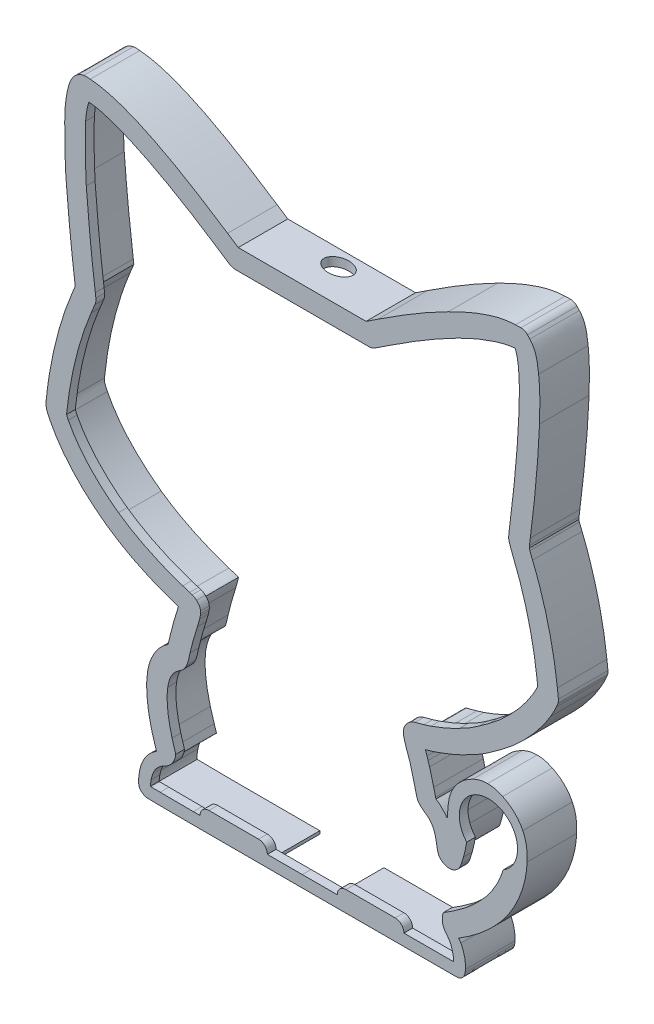
SolidWorks part; units mm, degrees
ref_plane "Front" through (0, 0, 0) normal (0, 0, 1) x (1, 0, 0)
ref_plane "Top" through (0, 0, 0) normal (0, 1, 0) x (1, 0, 0)
ref_plane "Right" through (0, 0, 0) normal (1, 0, 0) x (0, 0, -1)
sketch "Mech_Outlines_Cat" plane through (0, 0, 0) normal (0, 0, 1) x (1, 0, 0)
  line L0 (9.9633, 69.1549) -> (10.0093, 68.7865)
  line L1 (10.0093, 68.7865) -> (9.5041, 67.5722)
  line L4 (75.401, -1.0986) -> (48.9706, -1.125)
  line L6 (76.9457, 0.7665) -> (76.9132, 0.3114)
  line L8 (72.1076, 30.6075) -> (70.8601, 30.2154)
  line L10 (92.8011, 48.1756) -> (92.5648, 47.5932)
  line L12 (92.7273, 50.4965) -> (92.9034, 48.9145)
  line L15 (87.5993, 100.3815) -> (88.0029, 99.9501)
  line L18 (85.548, 100.8461) -> (86.4656, 100.8616)
  line L19 (61.947, 89.8796) -> (59.9011, 88.536)
  line L20 (59.9011, 88.536) -> (48.9353, 88.536)
  line L21 (48.9353, 88.536) -> (37.9736, 88.536)
  line L22 (37.9736, 88.536) -> (36.1471, 89.7448)
  line L26 (13.5479, 68.8251) -> (13.4504, 69.5965)
  line L29 (12.7494, 66.2211) -> (13.4097, 67.8086)
  line L31 (73.1045, 2.4142) -> (48.9672, 2.3905)
  line L35 (71.0037, 33.9449) -> (69.8057, 33.5683)
  line L36 (89.2861, 48.8458) -> (89.354, 49.0282)
  line L37 (89.354, 49.0282) -> (89.2335, 50.1084)
  line L43 (61.4513, 85.3482) -> (63.8765, 86.9418)
  line L46 (37.5165, 85.0205) -> (60.3549, 85.0205)
  line L48 (34.2062, 86.8145) -> (36.4133, 85.353)
  line L49 (11.9483, 69.4062) -> (11.9483, 69.4055)
  line L50 (11.9483, 69.4055) -> (12.0451, 68.6361)
  line L51 (12.0451, 68.6361) -> (11.9483, 69.4062)
  line L52 (12.0119, 68.3903) -> (11.3516, 66.8035)
  line L53 (11.3516, 66.8035) -> (12.0119, 68.3903)
  line L54 (48.9685, 0.8755) -> (74.9499, 0.9019)
  line L55 (74.9499, 0.9019) -> (74.9499, 0.9093)
  line L57 (68.5561, 31.6646) -> (68.5622, 31.6659)
  line L58 (68.5622, 31.6659) -> (68.5561, 31.6646)
  line L59 (70.2601, 32.1244) -> (71.5021, 32.5152)
  line L60 (71.5021, 32.5152) -> (70.2601, 32.1244)
  line L61 (90.7112, 48.3456) -> (90.9015, 48.8149)
  line L62 (90.9015, 48.8149) -> (90.7389, 50.275)
  line L64 (86.5414, 98.5841) -> (86.2848, 98.8577)
  line L65 (86.2848, 98.8577) -> (85.5825, 98.8462)
  line L67 (63.0455, 88.2075) -> (60.6203, 86.6147)
  line L68 (60.6203, 86.6147) -> (63.0455, 88.2075)
  line L69 (60.3548, 86.5354) -> (48.9353, 86.5354)
  line L70 (48.9353, 86.5354) -> (37.5165, 86.5354)
  line L71 (37.5165, 86.5354) -> (60.3548, 86.5354)
  line L72 (37.2497, 86.6154) -> (35.0426, 88.0768)
  line L73 (35.0426, 88.0768) -> (37.2497, 86.6154)
  line L74 (10.9053, 66.9894) -> (11.5659, 68.5759)
  line L75 (11.5659, 68.5759) -> (11.4685, 69.3451)
  line L77 (35.3096, 88.4796) -> (37.5166, 87.0182)
  line L78 (37.5166, 87.0182) -> (48.9356, 87.0182)
  line L79 (48.9356, 87.0182) -> (60.3546, 87.0182)
  line L80 (60.3546, 87.0182) -> (62.78, 88.6113)
  line L82 (85.5745, 99.329) -> (86.4912, 99.3449)
  line L83 (86.4912, 99.3449) -> (86.894, 98.9141)
  line L85 (91.2192, 50.3286) -> (91.3952, 48.7468)
  line L86 (91.3952, 48.7468) -> (91.1586, 48.1639)
  line L88 (71.6522, 32.0554) -> (70.4053, 31.6632)
  line L89 (70.4053, 31.6632) -> (71.6522, 32.0554)
  line L90 (75.4324, 0.8747) -> (75.3997, 0.419)
  line L91 (75.3997, 0.419) -> (48.9694, 0.3927)
  spline S0 degree 3 poles (11.483, 100.8711) (11.0606, 100.8073) (10.6358, 100.5764) (10.4224, 100.4329) knots 0 0 0 0 1 1 1 1
  spline S1 degree 3 poles (10.4224, 100.4329) (9.5693, 99.8591) (9.1825, 99.0134) (8.8872, 98.0538) knots 0 0 0 0 1 1 1 1
  spline S2 degree 3 poles (8.8872, 98.0538) (8.5918, 97.0942) (8.409, 95.9431) (8.2892, 94.5315) knots 0 0 0 0 1 1 1 1
  spline S3 degree 3 poles (8.2892, 94.5315) (8.1234, 92.5785) (8.2081, 86.8649) (8.4009, 84.4028) knots 0 0 0 0 1 1 1 1
  spline S4 degree 3 poles (8.4009, 84.4028) (8.8396, 78.8005) (9.255, 74.7491) (9.9633, 69.1549) knots 0 0 0 0 1 1 1 1
  spline S5 degree 3 poles (9.5041, 67.5722) (7.2088, 62.06) (5.6804, 55.8309) (5.0222, 49.3594) knots 0 0 0 0 1 1 1 1
  spline S6 degree 3 poles (5.0222, 49.3594) (4.9895, 49.0381) (4.966, 48.5524) (5.0953, 48.0957) knots 0 0 0 0 1 1 1 1
  spline S7 degree 3 poles (5.0953, 48.0957) (5.2247, 47.6389) (5.3974, 47.3215) (5.6717, 46.7656) knots 0 0 0 0 1 1 1 1
  spline S8 degree 3 poles (5.6717, 46.7656) (7.576, 42.9054) (11.0475, 39.1152) (15.3798, 36.0165) knots 0 0 0 0 1 1 1 1
  spline S9 degree 3 poles (15.3798, 36.0165) (18.6451, 33.681) (23.0339, 31.5595) (27.4027, 30.1754) knots 0 0 0 0 1 1 1 1
  spline S10 degree 3 poles (27.4027, 30.1754) (27.5208, 30.138) (27.5984, 30.11) (27.7102, 30.0738) knots 0 0 0 0 1 1 1 1
  spline S11 degree 3 poles (27.7102, 30.0738) (27.6776, 29.965) (27.6616, 29.8946) (27.6255, 29.7799) knots 0 0 0 0 1 1 1 1
  spline S12 degree 3 poles (27.6255, 29.7799) (26.9394, 27.5964) (26.6132, 26.4326) (26.2717, 24.9438) knots 0 0 0 0 1 1 1 1
  spline S13 degree 3 poles (26.2717, 24.9438) (26.0502, 23.9777) (25.9393, 23.5952) (25.9311, 23.548) knots 0 0 0 0 1 1 1 1
  spline S14 degree 3 poles (25.9311, 23.548) (25.888, 23.5182) (25.9087, 23.5331) (25.8268, 23.4775) knots 0 0 0 0 1 1 1 1
  spline S15 degree 3 poles (25.8268, 23.4775) (23.953, 22.205) (22.7972, 20.1517) (22.4163, 17.7109) knots 0 0 0 0 1 1 1 1
  spline S16 degree 3 poles (22.4163, 17.7109) (22.0353, 15.2701) (22.3385, 12.4089) (23.2222, 9.0796) knots 0 0 0 0 1 1 1 1
  spline S17 degree 3 poles (23.2222, 9.0796) (23.4031, 8.3979) (23.7033, 7.4032) (23.9238, 6.7519) knots 0 0 0 0 1 1 1 1
  spline S18 degree 3 poles (23.9238, 6.7519) (23.9349, 6.7191) (23.9414, 6.697) (23.9522, 6.6645) knots 0 0 0 0 1 1 1 1
  spline S19 degree 3 poles (23.9522, 6.6645) (22.447, 5.7656) (21.4163, 4.2188) (21.0638, 2.3763) knots 0 0 0 0 1 1 1 1
  spline S20 degree 3 poles (21.0638, 2.3763) (20.9716, 1.8941) (20.9139, 1.4626) (20.8884, 1.0936) knots 0 0 0 0 1 1 1 1
  spline S21 degree 3 poles (20.8884, 1.0936) (20.8757, 0.9091) (20.8691, 0.7457) (20.8796, 0.5552) knots 0 0 0 0 1 1 1 1
  spline S22 degree 3 poles (20.8796, 0.5552) (20.8848, 0.46) (20.8918, 0.3602) (20.925, 0.2078) knots 0 0 0 0 1 1 1 1
  spline S23 degree 3 poles (20.925, 0.2078) (20.9581, 0.0554) (20.9272, -0.1682) (21.3577, -0.5988) knots 0 0 0 0 1 1 1 1
  spline S24 degree 3 poles (21.3577, -0.5988) (21.358, -0.5991) (21.7141, -0.8678) (21.8101, -0.911) knots 0 0 0 0 1 1 1 1
  spline S25 degree 3 poles (21.8101, -0.911) (21.9062, -0.9542) (21.9665, -0.9718) (22.014, -0.9855) knots 0 0 0 0 1 1 1 1
  spline S26 degree 3 poles (22.014, -0.9855) (22.109, -1.013) (22.1542, -1.0197) (22.1921, -1.0261) knots 0 0 0 0 1 1 1 1
  spline S27 degree 3 poles (22.1921, -1.0261) (22.268, -1.0389) (22.3025, -1.0413) (22.3363, -1.0444) knots 0 0 0 0 1 1 1 1
  spline S28 degree 3 poles (22.3363, -1.0444) (22.404, -1.0505) (22.4538, -1.0532) (22.5131, -1.0559) knots 0 0 0 0 1 1 1 1
  spline S29 degree 3 poles (22.5131, -1.0559) (22.6317, -1.0613) (22.777, -1.0654) (22.9641, -1.0695) knots 0 0 0 0 1 1 1 1
  spline S30 degree 3 poles (22.9641, -1.0695) (23.3383, -1.0775) (23.8704, -1.0843) (24.5516, -1.0904) knots 0 0 0 0 1 1 1 1
  spline S31 degree 3 poles (24.5516, -1.0904) (25.9138, -1.1028) (27.8679, -1.1119) (30.2735, -1.1182) knots 0 0 0 0 1 1 1 1
  spline S32 degree 3 poles (30.2735, -1.1182) (35.0848, -1.1308) (41.7012, -1.1322) (48.9706, -1.125) knots 0 0 0 0 1 1 1 1
  spline S33 degree 3 poles (75.401, -1.0986) (76.1968, -1.0979) (76.8568, -0.4824) (76.9132, 0.3114) knots 0 0 0 0 1 1 1 1
  spline S34 degree 3 poles (76.9457, 0.7665) (77.0372, 2.0432) (76.723, 3.2035) (76.1696, 4.2997) knots 0 0 0 0 1 1 1 1
  spline S35 degree 3 poles (76.1696, 4.2997) (76.0699, 4.4972) (75.917, 4.6561) (75.8026, 4.8381) knots 0 0 0 0 1 1 1 1
  spline S36 degree 3 poles (75.8026, 4.8381) (76.938, 5.554) (78.3083, 6.4993) (79.2388, 7.2463) knots 0 0 0 0 1 1 1 1
  spline S37 degree 3 poles (79.2388, 7.2463) (80.6214, 8.3562) (82.2184, 9.9076) (83.1986, 11.1181) knots 0 0 0 0 1 1 1 1
  spline S38 degree 3 poles (83.1986, 11.1181) (85.8315, 14.3695) (87.3514, 18.1344) (87.5458, 22.0263) knots 0 0 0 0 1 1 1 1
  spline S39 degree 3 poles (87.5458, 22.0263) (87.6301, 23.7136) (87.413, 25.0337) (86.7907, 26.3206) knots 0 0 0 0 1 1 1 1
  spline S40 degree 3 poles (86.7907, 26.3206) (86.0786, 27.7931) (84.8934, 28.9158) (83.3381, 29.6573) knots 0 0 0 0 1 1 1 1
  spline S41 degree 3 poles (83.3381, 29.6573) (82.3647, 30.1215) (81.6667, 30.2831) (80.7572, 30.2831) knots 0 0 0 0 1 1 1 1
  spline S42 degree 3 poles (80.7572, 30.2831) (79.8502, 30.2831) (79.1466, 30.1205) (78.2081, 29.6709) knots 0 0 0 0 1 1 1 1
  spline S43 degree 3 poles (78.2081, 29.6709) (76.3488, 28.7802) (75.0037, 27.3447) (74.3567, 25.4842) knots 0 0 0 0 1 1 1 1
  spline S44 degree 3 poles (74.3567, 25.4842) (74.1097, 24.7741) (74.0008, 24.0369) (73.928, 22.8863) knots 0 0 0 0 1 1 1 1
  spline S45 degree 3 poles (73.928, 22.8863) (73.9025, 22.4844) (73.8623, 22.1248) (73.8237, 21.6856) knots 0 0 0 0 1 1 1 1
  spline S46 degree 3 poles (73.8237, 21.6856) (73.3014, 22.4054) (72.6973, 23.0512) (71.9423, 23.5399) knots 0 0 0 0 1 1 1 1
  spline S47 degree 3 poles (71.9423, 23.5399) (71.9244, 23.5515) (71.9146, 23.5621) (71.8963, 23.5751) knots 0 0 0 0 1 1 1 1
  spline S48 degree 3 poles (71.8963, 23.5751) (71.8672, 23.6884) (71.871, 23.6734) (71.8353, 23.8182) knots 0 0 0 0 1 1 1 1
  spline S49 degree 3 poles (71.8353, 23.8182) (71.7487, 24.1698) (71.6358, 24.6319) (71.5191, 25.1158) knots 0 0 0 0 1 1 1 1
  spline S50 degree 3 poles (71.5191, 25.1158) (71.2791, 26.1105) (70.9851, 27.2464) (70.8161, 27.8017) knots 0 0 0 0 1 1 1 1
  spline S51 degree 3 poles (70.8161, 27.8017) (70.728, 28.091) (70.6244, 28.3747) (70.5438, 28.6063) knots 0 0 0 0 1 1 1 1
  spline S52 degree 3 poles (70.5438, 28.6063) (70.3694, 29.1843) (70.4928, 28.732) (70.3651, 29.2002) knots 0 0 0 0 1 1 1 1
  spline S53 degree 3 poles (70.3651, 29.2002) (70.2466, 29.5242) (70.1775, 29.7352) (70.0786, 30.0081) knots 0 0 0 0 1 1 1 1
  spline S54 degree 3 poles (70.0786, 30.0081) (70.346, 30.0853) (70.5715, 30.1246) (70.8601, 30.2154) knots 0 0 0 0 1 1 1 1
  spline S55 degree 3 poles (72.1076, 30.6075) (72.1232, 30.6124) (72.1388, 30.6176) (72.1543, 30.6231) knots 0 0 0 0 1 1 1 1
  spline S56 degree 3 poles (72.1543, 30.6231) (74.0017, 31.2705) (75.8041, 32.0437) (77.5607, 32.9731) knots 0 0 0 0 1 1 1 1
  spline S57 degree 3 poles (77.5607, 32.9731) (79.0293, 33.7139) (80.2072, 34.4182) (81.3295, 35.2364) knots 0 0 0 0 1 1 1 1
  spline S58 degree 3 poles (81.3295, 35.2364) (81.6799, 35.4919) (82.4473, 36.05) (83.03, 36.4723) knots 0 0 0 0 1 1 1 1
  spline S59 degree 3 poles (83.03, 36.4723) (86.4287, 38.9357) (89.5328, 42.2594) (91.5069, 45.5913) knots 0 0 0 0 1 1 1 1
  spline S60 degree 3 poles (91.5069, 45.5913) (91.931, 46.307) (92.3303, 47.0154) (92.5648, 47.5932) knots 0 0 0 0 1 1 1 1
  spline S61 degree 3 poles (92.8011, 48.1756) (92.8961, 48.4095) (92.9313, 48.6635) (92.9034, 48.9145) knots 0 0 0 0 1 1 1 1
  spline S62 degree 3 poles (92.7273, 50.4965) (92.093, 56.1971) (90.5352, 62.3618) (88.458, 67.3501) knots 0 0 0 0 1 1 1 1
  spline S63 degree 3 poles (88.458, 67.3501) (88.2819, 67.7731) (88.1195, 68.1989) (88.009, 68.5183) knots 0 0 0 0 1 1 1 1
  spline S64 degree 3 poles (88.009, 68.5183) (87.9602, 68.6594) (87.9269, 68.7671) (87.9034, 68.8475) knots 0 0 0 0 1 1 1 1
  spline S65 degree 3 poles (87.9034, 68.8475) (87.9087, 68.8743) (87.9157, 69.0095) (87.944, 69.2707) knots 0 0 0 0 1 1 1 1
  spline S66 degree 3 poles (87.944, 69.2707) (87.9797, 69.6001) (88.0301, 70.0196) (88.0849, 70.4376) knots 0 0 0 0 1 1 1 1
  spline S67 degree 3 poles (88.0849, 70.4376) (88.8749, 76.4699) (89.458, 82.9958) (89.6676, 88.1723) knots 0 0 0 0 1 1 1 1
  spline S68 degree 3 poles (89.6676, 88.1723) (89.7866, 91.1127) (89.7373, 93.5646) (89.5098, 95.498) knots 0 0 0 0 1 1 1 1
  spline S69 degree 3 poles (89.5098, 95.498) (89.2822, 97.4314) (89.0358, 98.8455) (88.0029, 99.9501) knots 0 0 0 0 1 1 1 1
  spline S70 degree 3 poles (87.5993, 100.3815) (87.3062, 100.6945) (86.8944, 100.8689) (86.4656, 100.8616) knots 0 0 0 0 1 1 1 1
  spline S71 degree 3 poles (85.548, 100.8461) (82.5799, 100.7945) (78.7259, 99.412) (73.9849, 97.0061) knots 0 0 0 0 1 1 1 1
  spline S72 degree 3 poles (73.9849, 97.0061) (70.2358, 95.1037) (66.8131, 93.0759) (61.947, 89.8796) knots 0 0 0 0 1 1 1 1
  spline S73 degree 3 poles (36.1471, 89.7448) (25.7127, 96.6542) (18.0196, 100.4687) (12.5903, 100.8698) knots 0 0 0 0 1 1 1 1
  spline S74 degree 3 poles (12.5903, 100.8698) (12.1899, 100.8993) (11.9073, 100.9352) (11.483, 100.8711) knots 0 0 0 0 1 1 1 1
  spline S75 degree 3 poles (12.3912, 97.3542) (12.3443, 97.2626) (12.303, 97.2025) (12.2469, 97.0204) knots 0 0 0 0 1 1 1 1
  spline S76 degree 3 poles (12.2469, 97.0204) (12.0709, 96.4484) (11.8988, 95.4961) (11.7918, 94.2349) knots 0 0 0 0 1 1 1 1
  spline S77 degree 3 poles (11.7918, 94.2349) (11.6977, 93.1254) (11.7448, 86.7307) (11.9056, 84.6771) knots 0 0 0 0 1 1 1 1
  spline S78 degree 3 poles (11.9056, 84.6771) (12.3411, 79.1152) (12.7471, 75.151) (13.4504, 69.5965) knots 0 0 0 0 1 1 1 1
  spline S79 degree 3 poles (13.5479, 68.8251) (13.5911, 68.48) (13.5435, 68.1296) (13.4097, 67.8086) knots 0 0 0 0 1 1 1 1
  spline S80 degree 3 poles (12.7494, 66.2211) (10.6029, 61.0663) (9.1451, 55.1552) (8.5194, 49.0038) knots 0 0 0 0 1 1 1 1
  spline S81 degree 3 poles (8.5194, 49.0038) (8.6107, 48.7304) (8.7135, 48.5454) (8.8242, 48.3205) knots 0 0 0 0 1 1 1 1
  spline S82 degree 3 poles (8.8242, 48.3205) (10.3737, 45.1796) (13.4824, 41.6957) (17.425, 38.8758) knots 0 0 0 0 1 1 1 1
  spline S83 degree 3 poles (17.425, 38.8758) (20.2884, 36.8278) (24.4437, 34.8002) (28.4646, 33.5263) knots 0 0 0 0 1 1 1 1
  spline S84 degree 3 poles (28.4646, 33.5263) (28.9086, 33.3857) (29.3201, 33.2499) (29.6423, 33.1383) knots 0 0 0 0 1 1 1 1
  spline S85 degree 3 poles (29.6423, 33.1383) (29.8034, 33.0824) (29.9402, 33.0337) (30.0636, 32.9866) knots 0 0 0 0 1 1 1 1
  spline S86 degree 3 poles (30.0636, 32.9866) (30.3348, 32.8479) (30.345, 32.9735) (30.8302, 32.5477) knots 0 0 0 0 1 1 1 1
  spline S87 degree 3 poles (30.8302, 32.5477) (31.5389, 31.9208) (31.4655, 31.5074) (31.4932, 31.2982) knots 0 0 0 0 1 1 1 1
  spline S88 degree 3 poles (31.4932, 31.2982) (31.5209, 31.0891) (31.5132, 30.9861) (31.5088, 30.9) knots 0 0 0 0 1 1 1 1
  spline S89 degree 3 poles (31.5088, 30.9) (31.4999, 30.7278) (31.4832, 30.641) (31.4675, 30.5506) knots 0 0 0 0 1 1 1 1
  spline S90 degree 3 poles (31.4675, 30.5506) (31.4361, 30.3696) (31.3986, 30.2114) (31.3523, 30.0271) knots 0 0 0 0 1 1 1 1
  spline S91 degree 3 poles (31.3523, 30.0271) (31.2598, 29.6583) (31.1318, 29.2116) (30.9792, 28.7261) knots 0 0 0 0 1 1 1 1
  spline S92 degree 3 poles (30.9792, 28.7261) (30.304, 26.5777) (30.0201, 25.5633) (29.6979, 24.1581) knots 0 0 0 0 1 1 1 1
  spline S93 degree 3 poles (29.6979, 24.1581) (29.4602, 23.1218) (29.4196, 22.6757) (29.106, 21.9781) knots 0 0 0 0 1 1 1 1
  spline S94 degree 3 poles (29.106, 21.9781) (28.9491, 21.6294) (28.634, 21.2095) (28.3624, 20.9758) knots 0 0 0 0 1 1 1 1
  spline S95 degree 3 poles (28.3624, 20.9758) (28.0907, 20.7421) (27.9357, 20.6605) (27.8016, 20.5695) knots 0 0 0 0 1 1 1 1
  spline S96 degree 3 poles (27.8016, 20.5695) (26.7739, 19.8716) (26.1592, 18.895) (25.8898, 17.1691) knots 0 0 0 0 1 1 1 1
  spline S97 degree 3 poles (25.8898, 17.1691) (25.6204, 15.4432) (25.8158, 13.011) (26.6198, 9.9816) knots 0 0 0 0 1 1 1 1
  spline S98 degree 3 poles (26.6198, 9.9816) (26.7686, 9.4211) (27.0747, 8.4058) (27.253, 7.8788) knots 0 0 0 0 1 1 1 1
  spline S99 degree 3 poles (27.253, 7.8788) (27.3604, 7.5616) (27.457, 7.2611) (27.5321, 7.0133) knots 0 0 0 0 1 1 1 1
  spline S100 degree 3 poles (27.5321, 7.0133) (27.5696, 6.8894) (27.6017, 6.7802) (27.6303, 6.6727) knots 0 0 0 0 1 1 1 1
  spline S101 degree 3 poles (27.6303, 6.6727) (27.6445, 6.6189) (27.658, 6.5672) (27.6736, 6.4952) knots 0 0 0 0 1 1 1 1
  spline S102 degree 3 poles (27.6736, 6.4952) (27.6892, 6.4232) (27.7264, 6.4319) (27.7264, 6.0252) knots 0 0 0 0 1 1 1 1
  spline S103 degree 3 poles (27.7264, 6.0252) (27.7264, 5.2855) (27.4633, 5.0007) (27.3289, 4.8164) knots 0 0 0 0 1 1 1 1
  spline S104 degree 3 poles (27.3289, 4.8164) (27.1945, 4.6321) (27.0985, 4.5451) (27.0167, 4.471) knots 0 0 0 0 1 1 1 1
  spline S105 degree 3 poles (27.0167, 4.471) (26.8531, 4.3227) (26.7395, 4.2477) (26.6232, 4.1716) knots 0 0 0 0 1 1 1 1
  spline S106 degree 3 poles (26.6232, 4.1716) (26.3906, 4.0195) (26.1608, 3.8962) (25.8999, 3.7741) knots 0 0 0 0 1 1 1 1
  spline S107 degree 3 poles (25.8999, 3.7741) (25.3703, 3.5262) (25.0356, 3.0723) (24.7825, 2.4237) knots 0 0 0 0 1 1 1 1
  spline S108 degree 3 poles (24.7825, 2.4237) (26.1233, 2.4121) (27.9649, 2.4033) (30.283, 2.3973) knots 0 0 0 0 1 1 1 1
  spline S109 degree 3 poles (30.283, 2.3973) (35.0864, 2.3847) (41.7003, 2.3833) (48.9672, 2.3905) knots 0 0 0 0 1 1 1 1
  spline S110 degree 3 poles (73.1045, 2.4142) (73.0769, 2.5219) (73.0497, 2.6804) (73.032, 2.7156) knots 0 0 0 0 1 1 1 1
  spline S111 degree 3 poles (73.032, 2.7156) (72.9782, 2.8223) (72.6188, 3.3304) (72.6243, 3.3244) knots 0 0 0 0 1 1 1 1
  spline S112 degree 3 poles (72.6243, 3.3244) (72.4698, 3.4921) (72.3348, 3.651) (72.2071, 3.8208) knots 0 0 0 0 1 1 1 1
  spline S113 degree 3 poles (72.2071, 3.8208) (72.1433, 3.9057) (72.0824, 3.9884) (72.0046, 4.1175) knots 0 0 0 0 1 1 1 1
  spline S114 degree 3 poles (72.0046, 4.1175) (71.9657, 4.182) (71.9225, 4.2555) (71.8645, 4.387) knots 0 0 0 0 1 1 1 1
  spline S115 degree 3 poles (71.8645, 4.387) (71.8064, 4.5185) (71.6857, 4.6543) (71.6857, 5.2227) knots 0 0 0 0 1 1 1 1
  spline S116 degree 3 poles (71.6857, 5.2227) (71.6857, 6.4507) (72.1107, 6.4843) (72.2532, 6.6381) knots 0 0 0 0 1 1 1 1
  spline S117 degree 3 poles (72.2532, 6.6381) (72.3957, 6.7919) (72.4926, 6.8685) (72.5884, 6.9429) knots 0 0 0 0 1 1 1 1
  spline S118 degree 3 poles (72.5884, 6.9429) (72.78, 7.0916) (72.9566, 7.2019) (73.1593, 7.314) knots 0 0 0 0 1 1 1 1
  spline S119 degree 3 poles (73.1593, 7.314) (73.7969, 7.6666) (76.1056, 9.2386) (77.0378, 9.9871) knots 0 0 0 0 1 1 1 1
  spline S120 degree 3 poles (77.0378, 9.9871) (78.1798, 10.9038) (79.7667, 12.4646) (80.4674, 13.3299) knots 0 0 0 0 1 1 1 1
  spline S121 degree 3 poles (80.4674, 13.3299) (82.6845, 16.0679) (83.8803, 19.1042) (84.035, 22.2016) knots 0 0 0 0 1 1 1 1
  spline S122 degree 3 poles (84.035, 22.2016) (84.1045, 23.5921) (84.0348, 23.9446) (83.626, 24.79) knots 0 0 0 0 1 1 1 1
  spline S123 degree 3 poles (83.626, 24.79) (83.2192, 25.6311) (82.8655, 25.9878) (81.8252, 26.4838) knots 0 0 0 0 1 1 1 1
  spline S124 degree 3 poles (81.8252, 26.4838) (81.2872, 26.7156) (81.0774, 26.7776) (80.7572, 26.7675) knots 0 0 0 0 1 1 1 1
  spline S125 degree 3 poles (80.7572, 26.7675) (80.3846, 26.7559) (80.2768, 26.7725) (79.7265, 26.5007) knots 0 0 0 0 1 1 1 1
  spline S126 degree 3 poles (79.7265, 26.5007) (78.486, 25.8881) (78.0584, 25.4278) (77.6765, 24.3295) knots 0 0 0 0 1 1 1 1
  spline S127 degree 3 poles (77.6765, 24.3295) (77.5564, 23.9843) (77.5021, 23.7067) (77.4361, 22.6642) knots 0 0 0 0 1 1 1 1
  spline S128 degree 3 poles (77.4361, 22.6642) (77.3825, 21.8177) (77.2922, 20.7613) (77.216, 20.1456) knots 0 0 0 0 1 1 1 1
  spline S129 degree 3 poles (77.216, 20.1456) (77.1068, 19.2642) (76.8665, 18.2131) (76.6193, 17.2964) knots 0 0 0 0 1 1 1 1
  spline S130 degree 3 poles (76.6193, 17.2964) (76.4957, 16.8381) (76.3757, 16.4331) (76.2434, 16.0727) knots 0 0 0 0 1 1 1 1
  spline S131 degree 3 poles (76.2434, 16.0727) (76.1773, 15.8925) (76.1265, 15.7413) (75.978, 15.4801) knots 0 0 0 0 1 1 1 1
  spline S132 degree 3 poles (75.978, 15.4801) (75.9037, 15.3495) (75.8562, 15.1885) (75.4741, 14.8692) knots 0 0 0 0 1 1 1 1
  spline S133 degree 3 poles (75.4741, 14.8692) (75.2831, 14.7096) (74.9604, 14.4645) (74.3777, 14.4046) knots 0 0 0 0 1 1 1 1
  spline S134 degree 3 poles (74.3777, 14.4046) (73.7952, 14.3448) (73.0757, 14.6551) (72.7449, 14.9857) knots 0 0 0 0 1 1 1 1
  spline S135 degree 3 poles (72.7449, 14.9857) (72.2906, 15.4398) (72.3482, 15.5425) (72.3074, 15.6406) knots 0 0 0 0 1 1 1 1
  spline S136 degree 3 poles (72.3074, 15.6406) (72.2666, 15.7387) (72.2507, 15.79) (72.2369, 15.8343) knots 0 0 0 0 1 1 1 1
  spline S137 degree 3 poles (72.2369, 15.8343) (72.2094, 15.9228) (72.1979, 15.9729) (72.1855, 16.0246) knots 0 0 0 0 1 1 1 1
  spline S138 degree 3 poles (72.1855, 16.0246) (72.1605, 16.128) (72.1408, 16.223) (72.1191, 16.3327) knots 0 0 0 0 1 1 1 1
  spline S139 degree 3 poles (72.1191, 16.3327) (72.0758, 16.5523) (72.0285, 16.8191) (71.9816, 17.1102) knots 0 0 0 0 1 1 1 1
  spline S140 degree 3 poles (71.9816, 17.1102) (71.6753, 19.0097) (71.0994, 19.8987) (70.0325, 20.5891) knots 0 0 0 0 1 1 1 1
  spline S141 degree 3 poles (70.0325, 20.5891) (69.7931, 20.7441) (69.5856, 20.9015) (69.3817, 21.0862) knots 0 0 0 0 1 1 1 1
  spline S142 degree 3 poles (69.3817, 21.0862) (69.2798, 21.1786) (69.1796, 21.2748) (69.0614, 21.4154) knots 0 0 0 0 1 1 1 1
  spline S143 degree 3 poles (69.0614, 21.4154) (68.9432, 21.5559) (68.7775, 21.6627) (68.6083, 22.2423) knots 0 0 0 0 1 1 1 1
  spline S144 degree 3 poles (68.6083, 22.2423) (68.5273, 22.5197) (68.5105, 22.6184) (68.4221, 22.9771) knots 0 0 0 0 1 1 1 1
  spline S145 degree 3 poles (68.4221, 22.9771) (68.3336, 23.336) (68.2204, 23.8012) (68.1024, 24.2902) knots 0 0 0 0 1 1 1 1
  spline S146 degree 3 poles (68.1024, 24.2902) (67.875, 25.2327) (67.5535, 26.4474) (67.453, 26.7777) knots 0 0 0 0 1 1 1 1
  spline S147 degree 3 poles (67.453, 26.7777) (67.4074, 26.9275) (67.3143, 27.1888) (67.2234, 27.4502) knots 0 0 0 0 1 1 1 1
  spline S148 degree 3 poles (67.2234, 27.4502) (66.9188, 28.3231) (66.8258, 28.405) (66.4391, 29.8083) knots 0 0 0 0 1 1 1 1
  spline S149 degree 3 poles (66.4391, 29.8083) (66.3477, 30.1868) (66.228, 30.607) (66.3809, 31.3131) knots 0 0 0 0 1 1 1 1
  spline S150 degree 3 poles (66.3809, 31.3131) (66.5338, 32.0193) (67.4664, 33.0132) (68.2988, 33.1566) knots 0 0 0 0 1 1 1 1
  spline S151 degree 3 poles (68.2988, 33.1566) (68.817, 33.3027) (69.3264, 33.4196) (69.8057, 33.5683) knots 0 0 0 0 1 1 1 1
  spline S152 degree 3 poles (71.0037, 33.9449) (72.7016, 34.5406) (74.3396, 35.2437) (75.9292, 36.0856) knots 0 0 0 0 1 1 1 1
  spline S153 degree 3 poles (75.9292, 36.0856) (75.9413, 36.0918) (75.9535, 36.0979) (75.9658, 36.1039) knots 0 0 0 0 1 1 1 1
  spline S154 degree 3 poles (75.9658, 36.1039) (77.318, 36.7853) (78.298, 37.3764) (79.2585, 38.0767) knots 0 0 0 0 1 1 1 1
  spline S155 degree 3 poles (79.2585, 38.0767) (79.6152, 38.3367) (80.3813, 38.8927) (80.9671, 39.3173) knots 0 0 0 0 1 1 1 1
  spline S156 degree 3 poles (80.9671, 39.3173) (83.9613, 41.4875) (86.8182, 44.5738) (88.4824, 47.3825) knots 0 0 0 0 1 1 1 1
  spline S157 degree 3 poles (88.4824, 47.3825) (88.8421, 47.9896) (89.267, 48.8021) (89.2861, 48.8458) knots 0 0 0 0 1 1 1 1
  spline S158 degree 3 poles (89.2335, 50.1084) (88.6389, 55.4519) (87.1323, 61.3898) (85.2127, 65.9997) knots 0 0 0 0 1 1 1 1
  spline S159 degree 3 poles (85.2127, 65.9997) (85.0099, 66.4867) (84.8281, 66.9627) (84.6872, 67.3704) knots 0 0 0 0 1 1 1 1
  spline S160 degree 3 poles (84.6872, 67.3704) (84.6167, 67.5743) (84.5563, 67.7589) (84.505, 67.9413) knots 0 0 0 0 1 1 1 1
  spline S161 degree 3 poles (84.505, 67.9413) (84.4538, 68.1238) (84.376, 68.1393) (84.377, 68.7439) knots 0 0 0 0 1 1 1 1
  spline S162 degree 3 poles (84.377, 68.7439) (84.3777, 69.1646) (84.4103, 69.2873) (84.4495, 69.6493) knots 0 0 0 0 1 1 1 1
  spline S163 degree 3 poles (84.4495, 69.6493) (84.4887, 70.0113) (84.541, 70.4504) (84.5991, 70.8941) knots 0 0 0 0 1 1 1 1
  spline S164 degree 3 poles (84.5991, 70.8941) (85.3756, 76.823) (85.9517, 83.2829) (86.1554, 88.3145) knots 0 0 0 0 1 1 1 1
  spline S165 degree 3 poles (86.1554, 88.3145) (86.2696, 91.1338) (86.212, 93.4441) (86.0186, 95.0876) knots 0 0 0 0 1 1 1 1
  spline S166 degree 3 poles (86.0186, 95.0876) (85.8656, 96.3879) (85.577, 97.0842) (85.5033, 97.3177) knots 0 0 0 0 1 1 1 1
  spline S167 degree 3 poles (85.5033, 97.3177) (83.6546, 97.2527) (80.0158, 96.1251) (75.5757, 93.8719) knots 0 0 0 0 1 1 1 1
  spline S168 degree 3 poles (75.5757, 93.8719) (71.9546, 92.0344) (68.6811, 90.0977) (63.8765, 86.9418) knots 0 0 0 0 1 1 1 1
  spline S169 degree 3 poles (61.4513, 85.3482) (61.1256, 85.1344) (60.7445, 85.0205) (60.3549, 85.0205) knots 0 0 0 0 1 1 1 1
  spline S170 degree 3 poles (37.5165, 85.0205) (37.1241, 85.0206) (36.7404, 85.1362) (36.4133, 85.353) knots 0 0 0 0 1 1 1 1
  spline S171 degree 3 poles (34.2062, 86.8145) (24.0058, 93.5688) (16.3294, 97.0371) (12.3912, 97.3542) knots 0 0 0 0 1 1 1 1
  spline S172 degree 3 poles (11.781, 98.8929) (11.6989, 98.8805) (11.6904, 98.8747) (11.5392, 98.773) knots 0 0 0 0 1 1 1 1
  spline S173 degree 3 poles (11.5392, 98.773) (11.3117, 98.62) (11.0264, 98.205) (10.799, 97.466) knots 0 0 0 0 1 1 1 1
  spline S174 degree 3 poles (10.799, 97.466) (10.5715, 96.727) (10.3955, 95.6889) (10.2829, 94.3629) knots 0 0 0 0 1 1 1 1
  spline S175 degree 3 poles (10.2829, 94.3629) (10.1579, 92.8899) (10.2208, 86.7889) (10.3954, 84.5593) knots 0 0 0 0 1 1 1 1
  spline S176 degree 3 poles (10.3954, 84.5593) (10.8322, 78.9799) (11.2428, 74.9778) (11.9483, 69.4062) knots 0 0 0 0 1 1 1 1
  spline S177 degree 3 poles (12.0451, 68.6361) (12.0556, 68.5527) (12.0442, 68.468) (12.0119, 68.3903) knots 0 0 0 0 1 1 1 1
  spline S178 degree 3 poles (11.3516, 66.8035) (9.141, 61.4947) (7.6522, 55.4462) (7.0126, 49.1569) knots 0 0 0 0 1 1 1 1
  spline S179 degree 3 poles (7.0126, 49.1569) (6.9827, 48.8629) (6.9756, 48.7977) (7.02, 48.6408) knots 0 0 0 0 1 1 1 1
  spline S180 degree 3 poles (7.02, 48.6408) (7.0644, 48.484) (7.1951, 48.2006) (7.4663, 47.6507) knots 0 0 0 0 1 1 1 1
  spline S181 degree 3 poles (7.4663, 47.6507) (9.1687, 44.1999) (12.4335, 40.5839) (16.544, 37.6439) knots 0 0 0 0 1 1 1 1
  spline S182 degree 3 poles (16.544, 37.6439) (19.5805, 35.472) (23.836, 33.4038) (28.0068, 32.0825) knots 0 0 0 0 1 1 1 1
  spline S183 degree 3 poles (28.0068, 32.0825) (28.4395, 31.9454) (28.8425, 31.8126) (29.1466, 31.7073) knots 0 0 0 0 1 1 1 1
  spline S184 degree 3 poles (29.1466, 31.7073) (29.2986, 31.6546) (29.4255, 31.6084) (29.5231, 31.5711) knots 0 0 0 0 1 1 1 1
  spline S185 degree 3 poles (29.5231, 31.5711) (29.572, 31.5525) (29.6128, 31.5364) (29.6511, 31.5197) knots 0 0 0 0 1 1 1 1
  spline S186 degree 3 poles (29.6511, 31.5197) (29.6895, 31.503) (29.6782, 31.5452) (29.8272, 31.4133) knots 0 0 0 0 1 1 1 1
  spline S187 degree 3 poles (29.8272, 31.4133) (30.0009, 31.2598) (29.9843, 31.1559) (29.9918, 31.0991) knots 0 0 0 0 1 1 1 1
  spline S188 degree 3 poles (29.9918, 31.0991) (29.9993, 31.0423) (29.9974, 31.0089) (29.9959, 30.9779) knots 0 0 0 0 1 1 1 1
  spline S189 degree 3 poles (29.9959, 30.9779) (29.9927, 30.9158) (29.9848, 30.8663) (29.9749, 30.8093) knots 0 0 0 0 1 1 1 1
  spline S190 degree 3 poles (29.9749, 30.8093) (29.955, 30.6951) (29.9244, 30.5587) (29.8834, 30.3955) knots 0 0 0 0 1 1 1 1
  spline S191 degree 3 poles (29.8834, 30.3955) (29.8015, 30.069) (29.6798, 29.6416) (29.5347, 29.1798) knots 0 0 0 0 1 1 1 1
  spline S192 degree 3 poles (29.5347, 29.1798) (28.8548, 27.0163) (28.552, 25.938) (28.2215, 24.4968) knots 0 0 0 0 1 1 1 1
  spline S193 degree 3 poles (28.2215, 24.4968) (27.982, 23.4523) (27.8955, 22.9782) (27.7251, 22.5992) knots 0 0 0 0 1 1 1 1
  spline S194 degree 3 poles (27.7251, 22.5992) (27.6399, 22.4096) (27.512, 22.2416) (27.375, 22.1237) knots 0 0 0 0 1 1 1 1
  spline S195 degree 3 poles (27.375, 22.1237) (27.2379, 22.0059) (27.1094, 21.9299) (26.951, 21.8224) knots 0 0 0 0 1 1 1 1
  spline S196 degree 3 poles (26.951, 21.8224) (25.5588, 20.8769) (24.7106, 19.4367) (24.3931, 17.4027) knots 0 0 0 0 1 1 1 1
  spline S197 degree 3 poles (24.3931, 17.4027) (24.0756, 15.3688) (24.318, 12.7515) (25.1563, 9.5929) knots 0 0 0 0 1 1 1 1
  spline S198 degree 3 poles (25.1563, 9.5929) (25.319, 8.9802) (25.6222, 7.9738) (25.8187, 7.3932) knots 0 0 0 0 1 1 1 1
  spline S199 degree 3 poles (25.8187, 7.3932) (25.9213, 7.0899) (26.0141, 6.8004) (26.0828, 6.5738) knots 0 0 0 0 1 1 1 1
  spline S200 degree 3 poles (26.0828, 6.5738) (26.1171, 6.4605) (26.1457, 6.3632) (26.1668, 6.2839) knots 0 0 0 0 1 1 1 1
  spline S201 degree 3 poles (26.1668, 6.2839) (26.1773, 6.2443) (26.1857, 6.2095) (26.1932, 6.1749) knots 0 0 0 0 1 1 1 1
  spline S202 degree 3 poles (26.1932, 6.1749) (26.2007, 6.1402) (26.2115, 6.1301) (26.2115, 6.0252) knots 0 0 0 0 1 1 1 1
  spline S203 degree 3 poles (26.2115, 6.0252) (26.2115, 5.8398) (26.1445, 5.7629) (26.1051, 5.7089) knots 0 0 0 0 1 1 1 1
  spline S204 degree 3 poles (26.1051, 5.7089) (26.0658, 5.655) (26.0323, 5.6228) (25.9995, 5.5931) knots 0 0 0 0 1 1 1 1
  spline S205 degree 3 poles (25.9995, 5.5931) (25.9339, 5.5337) (25.8695, 5.4881) (25.795, 5.4394) knots 0 0 0 0 1 1 1 1
  spline S206 degree 3 poles (25.795, 5.4394) (25.6459, 5.342) (25.4618, 5.2416) (25.2579, 5.1462) knots 0 0 0 0 1 1 1 1
  spline S207 degree 3 poles (25.2579, 5.1462) (24.0849, 4.5973) (23.3271, 3.5577) (23.0291, 2.0004) knots 0 0 0 0 1 1 1 1
  spline S208 degree 3 poles (23.0291, 2.0004) (22.9503, 1.5884) (22.9029, 1.2177) (22.8849, 0.9561) knots 0 0 0 0 1 1 1 1
  spline S209 degree 3 poles (22.8849, 0.9561) (22.8842, 0.9464) (22.8848, 0.9439) (22.8842, 0.9344) knots 0 0 0 0 1 1 1 1
  spline S210 degree 3 poles (22.8842, 0.9344) (22.9308, 0.9331) (22.9528, 0.9324) (23.0075, 0.931) knots 0 0 0 0 1 1 1 1
  spline S211 degree 3 poles (23.0075, 0.931) (23.3653, 0.9233) (23.8929, 0.9161) (24.5698, 0.91) knots 0 0 0 0 1 1 1 1
  spline S212 degree 3 poles (24.5698, 0.91) (25.9236, 0.8977) (27.8755, 0.8885) (30.2789, 0.8822) knots 0 0 0 0 1 1 1 1
  spline S213 degree 3 poles (30.2789, 0.8822) (35.0857, 0.8696) (41.7005, 0.8683) (48.9685, 0.8755) knots 0 0 0 0 1 1 1 1
  spline S214 degree 3 poles (74.9499, 0.9093) (74.9839, 1.3833) (74.679, 2.8132) (74.3838, 3.3982) knots 0 0 0 0 1 1 1 1
  spline S215 degree 3 poles (74.3838, 3.3982) (74.2408, 3.6814) (73.9074, 4.1663) (73.7377, 4.3504) knots 0 0 0 0 1 1 1 1
  spline S216 degree 3 poles (73.7377, 4.3504) (73.6148, 4.4837) (73.5045, 4.6158) (73.4173, 4.7317) knots 0 0 0 0 1 1 1 1
  spline S217 degree 3 poles (73.4173, 4.7317) (73.3738, 4.7896) (73.3368, 4.8423) (73.3022, 4.8996) knots 0 0 0 0 1 1 1 1
  spline S218 degree 3 poles (73.3022, 4.8996) (73.2849, 4.9283) (73.2683, 4.9573) (73.2501, 4.9985) knots 0 0 0 0 1 1 1 1
  spline S219 degree 3 poles (73.2501, 4.9985) (73.2319, 5.0397) (73.2006, 5.08) (73.2006, 5.2226) knots 0 0 0 0 1 1 1 1
  spline S220 degree 3 poles (73.2006, 5.2226) (73.2006, 5.53) (73.3123, 5.5531) (73.3638, 5.6087) knots 0 0 0 0 1 1 1 1
  spline S221 degree 3 poles (73.3638, 5.6087) (73.4153, 5.6643) (73.464, 5.7046) (73.5176, 5.7461) knots 0 0 0 0 1 1 1 1
  spline S222 degree 3 poles (73.5176, 5.7461) (73.6247, 5.8293) (73.7509, 5.9105) (73.8921, 5.9886) knots 0 0 0 0 1 1 1 1
  spline S223 degree 3 poles (73.8921, 5.9886) (74.7442, 6.4598) (76.9432, 7.9688) (77.986, 8.8059) knots 0 0 0 0 1 1 1 1
  spline S224 degree 3 poles (77.986, 8.8059) (79.2315, 9.8059) (80.8233, 11.3629) (81.6444, 12.3769) knots 0 0 0 0 1 1 1 1
  spline S225 degree 3 poles (81.6444, 12.3769) (84.0407, 15.3362) (85.3761, 18.6867) (85.5479, 22.1264) knots 0 0 0 0 1 1 1 1
  spline S226 degree 3 poles (85.5479, 22.1264) (85.6238, 23.6448) (85.4907, 24.4133) (84.9899, 25.4489) knots 0 0 0 0 1 1 1 1
  spline S227 degree 3 poles (84.9899, 25.4489) (84.4516, 26.5621) (83.7395, 27.2493) (82.4774, 27.8511) knots 0 0 0 0 1 1 1 1
  spline S228 degree 3 poles (82.4774, 27.8511) (81.5233, 28.3059) (81.6351, 28.2824) (80.7572, 28.2824) knots 0 0 0 0 1 1 1 1
  spline S229 degree 3 poles (80.7572, 28.2824) (79.8832, 28.2824) (79.9881, 28.3054) (79.0722, 27.8666) knots 0 0 0 0 1 1 1 1
  spline S230 degree 3 poles (79.0722, 27.8666) (77.561, 27.1427) (76.7423, 26.2539) (76.2461, 24.8272) knots 0 0 0 0 1 1 1 1
  spline S231 degree 3 poles (76.2461, 24.8272) (76.0714, 24.3247) (75.9934, 23.8487) (75.9245, 22.7596) knots 0 0 0 0 1 1 1 1
  spline S232 degree 3 poles (75.9245, 22.7596) (75.8729, 21.9449) (75.78, 20.871) (75.7132, 20.3317) knots 0 0 0 0 1 1 1 1
  spline S233 degree 3 poles (75.7132, 20.3317) (75.6218, 19.5944) (75.3897, 18.5537) (75.1572, 17.6912) knots 0 0 0 0 1 1 1 1
  spline S234 degree 3 poles (75.1572, 17.6912) (75.0409, 17.2599) (74.9253, 16.8775) (74.8212, 16.5941) knots 0 0 0 0 1 1 1 1
  spline S235 degree 3 poles (74.8212, 16.5941) (74.7692, 16.4524) (74.7246, 16.3402) (74.6614, 16.229) knots 0 0 0 0 1 1 1 1
  spline S236 degree 3 poles (74.6614, 16.229) (74.6298, 16.1735) (74.6061, 16.1175) (74.5029, 16.0313) knots 0 0 0 0 1 1 1 1
  spline S237 degree 3 poles (74.5029, 16.0313) (74.4513, 15.9882) (74.3681, 15.9264) (74.2226, 15.9114) knots 0 0 0 0 1 1 1 1
  spline S238 degree 3 poles (74.2226, 15.9114) (74.077, 15.8965) (73.8993, 15.9733) (73.8156, 16.057) knots 0 0 0 0 1 1 1 1
  spline S239 degree 3 poles (73.8156, 16.057) (73.7056, 16.1672) (73.7172, 16.1949) (73.7058, 16.2223) knots 0 0 0 0 1 1 1 1
  spline S240 degree 3 poles (73.7058, 16.2223) (73.6944, 16.2497) (73.6887, 16.2671) (73.6835, 16.2839) knots 0 0 0 0 1 1 1 1
  spline S241 degree 3 poles (73.6835, 16.2839) (73.673, 16.3175) (73.6658, 16.3466) (73.6577, 16.3801) knots 0 0 0 0 1 1 1 1
  spline S242 degree 3 poles (73.6577, 16.3801) (73.6416, 16.447) (73.6241, 16.5279) (73.6049, 16.6252) knots 0 0 0 0 1 1 1 1
  spline S243 degree 3 poles (73.6049, 16.6252) (73.5665, 16.8199) (73.5214, 17.0752) (73.4769, 17.3512) knots 0 0 0 0 1 1 1 1
  spline S244 degree 3 poles (73.4769, 17.3512) (73.125, 19.5336) (72.2933, 20.9296) (70.8554, 21.8602) knots 0 0 0 0 1 1 1 1
  spline S245 degree 3 poles (70.8554, 21.8602) (70.6855, 21.9702) (70.5289, 22.09) (70.3982, 22.2083) knots 0 0 0 0 1 1 1 1
  spline S246 degree 3 poles (70.3982, 22.2083) (70.3329, 22.2675) (70.2744, 22.326) (70.2201, 22.3905) knots 0 0 0 0 1 1 1 1
  spline S247 degree 3 poles (70.2201, 22.3905) (70.1658, 22.455) (70.109, 22.5067) (70.0623, 22.6668) knots 0 0 0 0 1 1 1 1
  spline S248 degree 3 poles (70.0623, 22.6668) (70.0312, 22.7735) (69.98, 22.9842) (69.8923, 23.34) knots 0 0 0 0 1 1 1 1
  spline S249 degree 3 poles (69.8923, 23.34) (69.8047, 23.6958) (69.6922, 24.1596) (69.5747, 24.6464) knots 0 0 0 0 1 1 1 1
  spline S250 degree 3 poles (69.5747, 24.6464) (69.3419, 25.6114) (69.0322, 26.792) (68.9022, 27.2192) knots 0 0 0 0 1 1 1 1
  spline S251 degree 3 poles (68.9022, 27.2192) (68.8383, 27.4291) (68.7408, 27.7) (68.6543, 27.9486) knots 0 0 0 0 1 1 1 1
  spline S252 degree 3 poles (68.6543, 27.9486) (68.3687, 28.7021) (68.1356, 29.2641) (67.9114, 30.1645) knots 0 0 0 0 1 1 1 1
  spline S253 degree 3 poles (67.9114, 30.1645) (67.8452, 30.4388) (67.7981, 30.7015) (67.8613, 30.9934) knots 0 0 0 0 1 1 1 1
  spline S254 degree 3 poles (67.8613, 30.9934) (67.9245, 31.2853) (68.2206, 31.6068) (68.5561, 31.6646) knots 0 0 0 0 1 1 1 1
  spline S255 degree 3 poles (68.5622, 31.6659) (68.7537, 31.6964) (69.5891, 31.9134) (70.2601, 32.1244) knots 0 0 0 0 1 1 1 1
  spline S256 degree 3 poles (71.5021, 32.5152) (71.5038, 32.5159) (71.5058, 32.5159) (71.5075, 32.5166) knots 0 0 0 0 1 1 1 1
  spline S257 degree 3 poles (71.5075, 32.5166) (73.2692, 33.1348) (74.9773, 33.8677) (76.6382, 34.7474) knots 0 0 0 0 1 1 1 1
  spline S258 degree 3 poles (76.6382, 34.7474) (76.641, 34.7491) (76.6441, 34.7505) (76.6471, 34.7521) knots 0 0 0 0 1 1 1 1
  spline S259 degree 3 poles (76.6471, 34.7521) (78.0524, 35.4603) (79.1192, 36.1006) (80.1511, 36.8529) knots 0 0 0 0 1 1 1 1
  spline S260 degree 3 poles (80.1511, 36.8529) (80.5051, 37.111) (81.2712, 37.6686) (81.8557, 38.0923) knots 0 0 0 0 1 1 1 1
  spline S261 degree 3 poles (81.8557, 38.0923) (85.0241, 40.3888) (87.9877, 43.5771) (89.7854, 46.6112) knots 0 0 0 0 1 1 1 1
  spline S262 degree 3 poles (89.7854, 46.6112) (90.1728, 47.2651) (90.6143, 48.1069) (90.7112, 48.3456) knots 0 0 0 0 1 1 1 1
  spline S263 degree 3 poles (90.7389, 50.275) (90.1273, 55.7724) (88.598, 61.8085) (86.6105, 66.5814) knots 0 0 0 0 1 1 1 1
  spline S264 degree 3 poles (86.6105, 66.5814) (86.4192, 67.0409) (86.246, 67.4951) (86.1182, 67.8648) knots 0 0 0 0 1 1 1 1
  spline S265 degree 3 poles (86.1182, 67.8648) (86.0543, 68.0496) (86.0017, 68.2122) (85.9631, 68.3497) knots 0 0 0 0 1 1 1 1
  spline S266 degree 3 poles (85.9631, 68.3497) (85.9244, 68.4872) (85.8917, 68.5594) (85.892, 68.7405) knots 0 0 0 0 1 1 1 1
  spline S267 degree 3 poles (85.892, 68.7405) (85.8923, 68.9119) (85.9172, 69.1381) (85.955, 69.4861) knots 0 0 0 0 1 1 1 1
  spline S268 degree 3 poles (85.955, 69.4861) (85.9926, 69.834) (86.0446, 70.265) (86.1012, 70.6977) knots 0 0 0 0 1 1 1 1
  spline S269 degree 3 poles (86.1012, 70.6977) (86.8835, 76.6711) (87.4621, 83.1595) (87.6684, 88.2536) knots 0 0 0 0 1 1 1 1
  spline S270 degree 3 poles (87.6684, 88.2536) (87.7846, 91.125) (87.7309, 93.4959) (87.5227, 95.2643) knots 0 0 0 0 1 1 1 1
  spline S271 degree 3 poles (87.5227, 95.2643) (87.3146, 97.0327) (86.9017, 98.1988) (86.5414, 98.5841) knots 0 0 0 0 1 1 1 1
  spline S272 degree 3 poles (85.5825, 98.8462) (83.2681, 98.806) (79.4999, 97.5615) (74.8903, 95.2223) knots 0 0 0 0 1 1 1 1
  spline S273 degree 3 poles (74.8903, 95.2223) (71.2141, 93.3568) (67.8765, 91.3809) (63.0455, 88.2075) knots 0 0 0 0 1 1 1 1
  spline S274 degree 3 poles (60.6203, 86.6147) (60.5415, 86.5629) (60.4492, 86.5354) (60.3548, 86.5354) knots 0 0 0 0 1 1 1 1
  spline S275 degree 3 poles (37.5165, 86.5354) (37.4216, 86.5353) (37.3288, 86.5631) (37.2497, 86.6154) knots 0 0 0 0 1 1 1 1
  spline S276 degree 3 poles (35.0426, 88.0768) (24.715, 94.9154) (17.014, 98.5369) (12.4426, 98.8746) knots 0 0 0 0 1 1 1 1
  spline S277 degree 3 poles (12.4426, 98.8746) (12.0618, 98.9028) (11.8624, 98.9052) (11.781, 98.8929) knots 0 0 0 0 1 1 1 1
  spline S278 degree 3 poles (22.5543, 2.0915) (22.8743, 3.7639) (23.7352, 4.9669) (25.0536, 5.5838) knots 0 0 0 0 1 1 1 1
  spline S279 degree 3 poles (25.0536, 5.5838) (25.4249, 5.7576) (25.7287, 5.9564) (25.7287, 6.0256) knots 0 0 0 0 1 1 1 1
  spline S280 degree 3 poles (25.7287, 6.0256) (25.7287, 6.0948) (25.5632, 6.6404) (25.3609, 7.238) knots 0 0 0 0 1 1 1 1
  spline S281 degree 3 poles (25.3609, 7.238) (25.1586, 7.8357) (24.8564, 8.8396) (24.6894, 9.469) knots 0 0 0 0 1 1 1 1
  spline S282 degree 3 poles (24.6894, 9.469) (22.9907, 15.8686) (23.6624, 20.1728) (26.6795, 22.2217) knots 0 0 0 0 1 1 1 1
  spline S283 degree 3 poles (26.6795, 22.2217) (27.344, 22.6729) (27.2709, 22.5103) (27.7511, 24.6043) knots 0 0 0 0 1 1 1 1
  spline S284 degree 3 poles (27.7511, 24.6043) (28.0842, 26.057) (28.3922, 27.1563) (29.0736, 29.3246) knots 0 0 0 0 1 1 1 1
  spline S285 degree 3 poles (29.0736, 29.3246) (29.3591, 30.233) (29.5542, 31.0103) (29.5071, 31.0519) knots 0 0 0 0 1 1 1 1
  spline S286 degree 3 poles (29.5071, 31.0519) (29.4601, 31.0936) (28.7194, 31.3501) (27.8612, 31.622) knots 0 0 0 0 1 1 1 1
  spline S287 degree 3 poles (27.8612, 31.622) (23.6426, 32.9585) (19.3544, 35.0396) (16.2626, 37.251) knots 0 0 0 0 1 1 1 1
  spline S288 degree 3 poles (16.2626, 37.251) (12.0986, 40.2293) (8.7842, 43.8871) (7.0331, 47.4367) knots 0 0 0 0 1 1 1 1
  spline S289 degree 3 poles (7.0331, 47.4367) (6.4891, 48.5393) (6.4706, 48.6047) (6.5317, 49.2058) knots 0 0 0 0 1 1 1 1
  spline S290 degree 3 poles (6.5317, 49.2058) (7.1759, 55.5391) (8.6742, 61.6314) (10.9053, 66.9894) knots 0 0 0 0 1 1 1 1
  spline S291 degree 3 poles (11.4685, 69.3451) (10.7624, 74.9222) (10.3512, 78.9367) (9.9139, 84.5216) knots 0 0 0 0 1 1 1 1
  spline S292 degree 3 poles (9.9139, 84.5216) (9.7349, 86.8074) (9.6665, 92.8149) (9.8014, 94.4038) knots 0 0 0 0 1 1 1 1
  spline S293 degree 3 poles (9.8014, 94.4038) (10.0299, 97.0971) (10.5123, 98.6644) (11.2695, 99.1737) knots 0 0 0 0 1 1 1 1
  spline S294 degree 3 poles (11.2695, 99.1737) (11.6019, 99.3972) (11.7071, 99.4131) (12.4782, 99.3562) knots 0 0 0 0 1 1 1 1
  spline S295 degree 3 poles (12.4782, 99.3562) (17.2568, 99.0032) (24.9562, 95.3353) (35.3096, 88.4796) knots 0 0 0 0 1 1 1 1
  spline S296 degree 3 poles (62.78, 88.6113) (67.6195, 91.7902) (70.9778, 93.7789) (74.6716, 95.6533) knots 0 0 0 0 1 1 1 1
  spline S297 degree 3 poles (74.6716, 95.6533) (79.313, 98.0086) (83.1023, 99.286) (85.5745, 99.329) knots 0 0 0 0 1 1 1 1
  spline S298 degree 3 poles (86.894, 98.9141) (87.9393, 97.7962) (88.385, 94.0098) (88.1512, 88.2336) knots 0 0 0 0 1 1 1 1
  spline S299 degree 3 poles (88.1512, 88.2336) (87.9441, 83.1197) (87.364, 76.6222) (86.5798, 70.6345) knots 0 0 0 0 1 1 1 1
  spline S300 degree 3 poles (86.5798, 70.6345) (86.4674, 69.7763) (86.3752, 68.9237) (86.3748, 68.7398) knots 0 0 0 0 1 1 1 1
  spline S301 degree 3 poles (86.3748, 68.7398) (86.3745, 68.5559) (86.6813, 67.6681) (87.0565, 66.7668) knots 0 0 0 0 1 1 1 1
  spline S302 degree 3 poles (87.0565, 66.7668) (89.0657, 61.9419) (90.602, 55.875) (91.2192, 50.3286) knots 0 0 0 0 1 1 1 1
  spline S303 degree 3 poles (91.1586, 48.1639) (91.0285, 47.8433) (90.5978, 47.0338) (90.2015, 46.3649) knots 0 0 0 0 1 1 1 1
  spline S304 degree 3 poles (90.2015, 46.3649) (88.3612, 43.2589) (85.3637, 40.0375) (82.1396, 37.7007) knots 0 0 0 0 1 1 1 1
  spline S305 degree 3 poles (82.1396, 37.7007) (81.5556, 37.2774) (80.7888, 36.7204) (80.4357, 36.4629) knots 0 0 0 0 1 1 1 1
  spline S306 degree 3 poles (80.4357, 36.4629) (79.3811, 35.6941) (78.2868, 35.0378) (76.8646, 34.3211) knots 0 0 0 0 1 1 1 1
  spline S307 degree 3 poles (76.8646, 34.3211) (75.1759, 33.4267) (73.4397, 32.6819) (71.6522, 32.0554) knots 0 0 0 0 1 1 1 1
  spline S308 degree 3 poles (70.4053, 31.6632) (69.7195, 31.4475) (68.9243, 31.2338) (68.6382, 31.1884) knots 0 0 0 0 1 1 1 1
  spline S309 degree 3 poles (68.6382, 31.1884) (67.9304, 31.0665) (68.5596, 29.7193) (68.94, 28.679) knots 0 0 0 0 1 1 1 1
  spline S310 degree 3 poles (68.94, 28.679) (69.0307, 28.4305) (69.2248, 27.8183) (69.3642, 27.3601) knots 0 0 0 0 1 1 1 1
  spline S311 degree 3 poles (69.3642, 27.3601) (69.5037, 26.9019) (69.8097, 25.7317) (70.0443, 24.7595) knots 0 0 0 0 1 1 1 1
  spline S312 degree 3 poles (70.0443, 24.7595) (70.2788, 23.7874) (70.4956, 22.9068) (70.526, 22.8027) knots 0 0 0 0 1 1 1 1
  spline S313 degree 3 poles (70.526, 22.8027) (70.5564, 22.6986) (70.8228, 22.457) (71.1181, 22.266) knots 0 0 0 0 1 1 1 1
  spline S314 degree 3 poles (71.1181, 22.266) (72.6744, 21.2587) (73.5873, 19.7014) (73.9538, 17.4287) knots 0 0 0 0 1 1 1 1
  spline S315 degree 3 poles (73.9538, 17.4287) (74.0412, 16.8863) (74.1326, 16.4227) (74.1568, 16.3985) knots 0 0 0 0 1 1 1 1
  spline S316 degree 3 poles (74.1568, 16.3985) (74.3156, 16.2397) (75.0624, 19.0086) (75.2337, 20.3914) knots 0 0 0 0 1 1 1 1
  spline S317 degree 3 poles (75.2337, 20.3914) (75.2975, 20.9063) (75.3914, 21.9859) (75.4424, 22.7904) knots 0 0 0 0 1 1 1 1
  spline S318 degree 3 poles (75.4424, 22.7904) (75.5123, 23.8944) (75.5975, 24.4329) (75.7897, 24.9855) knots 0 0 0 0 1 1 1 1
  spline S319 degree 3 poles (75.7897, 24.9855) (76.3222, 26.5169) (77.2683, 27.5376) (78.8636, 28.3018) knots 0 0 0 0 1 1 1 1
  spline S320 degree 3 poles (78.8636, 28.3018) (79.7849, 28.7432) (79.875, 28.7652) (80.7569, 28.7652) knots 0 0 0 0 1 1 1 1
  spline S321 degree 3 poles (80.7569, 28.7652) (81.6424, 28.7652) (81.7267, 28.7444) (82.6855, 28.2872) knots 0 0 0 0 1 1 1 1
  spline S322 degree 3 poles (82.6855, 28.2872) (84.0184, 27.6517) (84.8444, 26.8593) (85.4246, 25.6593) knots 0 0 0 0 1 1 1 1
  spline S323 degree 3 poles (85.4246, 25.6593) (85.9548, 24.563) (86.1083, 23.6615) (86.0304, 22.1023) knots 0 0 0 0 1 1 1 1
  spline S324 degree 3 poles (86.0304, 22.1023) (85.8531, 18.5534) (84.4733, 15.1028) (82.0199, 12.0731) knots 0 0 0 0 1 1 1 1
  spline S325 degree 3 poles (82.0199, 12.0731) (81.1603, 11.0116) (79.5673, 9.456) (78.2886, 8.4295) knots 0 0 0 0 1 1 1 1
  spline S326 degree 3 poles (78.2886, 8.4295) (77.2107, 7.564) (75.046, 6.0753) (74.1255, 5.5662) knots 0 0 0 0 1 1 1 1
  spline S327 degree 3 poles (74.1255, 5.5662) (73.8823, 5.4318) (73.6834, 5.2771) (73.6834, 5.2225) knots 0 0 0 0 1 1 1 1
  spline S328 degree 3 poles (73.6834, 5.2225) (73.6834, 5.1679) (73.8679, 4.923) (74.0935, 4.6783) knots 0 0 0 0 1 1 1 1
  spline S329 degree 3 poles (74.0935, 4.6783) (74.3191, 4.4335) (74.644, 3.9554) (74.8154, 3.6158) knots 0 0 0 0 1 1 1 1
  spline S330 degree 3 poles (74.8154, 3.6158) (75.173, 2.9074) (75.4802, 1.5425) (75.4324, 0.8747) knots 0 0 0 0 1 1 1 1
  spline S331 degree 3 poles (48.9694, 0.3927) (34.4327, 0.3783) (22.5078, 0.3978) (22.4315, 0.4741) knots 0 0 0 0 1 1 1 1
  spline S332 degree 3 poles (22.4315, 0.4741) (22.3552, 0.5504) (22.3902, 1.2336) (22.5543, 2.0915) knots 0 0 0 0 1 1 1 1
extrude "Boss-Extrude1" add sketch "Mech_Outlines_Cat" against normal blind 1.5 contours S276 S277 S172 S173 S174 S175 S176 L51 S177 L52 S178 S179 S180 S181 S182 S183 S184 S185 S186 S187 S188 S189 S190 S191 S192 S193 S194 S195 S196 S197 S198 S199 S200 S201 S202 S203 S204 S205 S206 S207 S208 S209 S210 S211 S212 S213 L54 L55 S214 S215 S216 | S332 S331 L91 L90 S330 S329 S328 S327 S326 S325 S324 S323 S322 S321 S320 S319 S318 S317 S316 S315 S314 S313 S312 S311 S310 S309 S308 L88 S307 S306 S305 S304 S303 L86 L85 S302 S301 S300 S299 S298 L83 L82 S297 S296 L80 L79 L78 L77 S295 S294 S293 | S73 S74 S0 S1 S2 S3 S4 L0 L1 S5 S6 S7 S8 S9 S10 S11 S12 S13 S14 S15 S16 S17 S18 S19 S20 S21 S22 S23 S24 S25 S26 S27 S28 S29 S30 S31 S32 L4 S33 L6 S34 S35 S36 S37 S38 S39 S40 S41 S42 S43 S44 region at (10.4216, 76.9059, 0) region at (12.3555, 77.1041, 0) region at (11.356, 67.7325, 0)
extrude "Boss-Extrude2" add sketch "Mech_Outlines_Cat<12>" against normal offset from surface (8.5 mm away) 7 contours S73 S74 S0 S1 S2 S3 S4 L0 L1 S5 S6 S7 S8 S9 S10 S11 S12 S13 S14 S15 S16 S17 S18 S19 S20 S21 S22 S23 S24 S25 S26 S27 S28 S29 S30 S31 S32 L4 S33 L6 S34 S35 S36 S37 S38 S39 S40 S41 S42 S43 S44 region at (10.4216, 76.9059, 0) up to face at (56.1988, 34.6226, -1.5) offset beyond the face yes
sketch "Mech_Outlines_Cat<12>" plane through (0, 0, 0) normal (0, 0, 1) x (1, 0, 0) same geometry as "Mech_Outlines_Cat"
sketch "Sketch1" plane through (0, 0, 0) normal (0, 0, 1) x (1, 0, 0)
  line L0 (48.9685, 0.8755) -> (54.9685, 0.8816)
  line L1 (73.1593, 7.314) -> (66.3997, 7.314)
  line L2 (42.9685, 0.8715) -> (42.9685, 7.8788)
  line L3 (54.9685, 0.8816) -> (54.9685, 7.8788)
  line L4 (66.3997, 7.314) -> (66.3997, 0.8932)
  line L5 (66.3997, 0.8932) -> (74.9499, 0.9019)
  line L6 (42.9685, 7.8788) -> (54.9685, 7.8788)
  line L7 (54.9685, 0.8816) -> (48.9685, 0.8755)
  line L8 (27.253, 7.8788) -> (31.4315, 7.8788)
  line L9 (48.9685, 0.8755) -> (74.9499, 0.9019) construction
  line L10 (31.4315, 7.8788) -> (31.4315, 0.8795)
  line L11 (74.9499, 0.9019) -> (74.9499, 0.9093) construction
  line L12 (74.9499, 0.9019) -> (74.9499, 0.9093)
  arc A0 (73.1593, 7.314) -> (73.7377, 4.3504) centre (75.8546, 6.3017) ccw
  arc A1 (25.795, 5.4394) -> (27.253, 7.8788) centre (24.0181, 8.1569) ccw
  spline S1 degree 3 poles (-1791.9689, -828.2619) (1856.5117, 911.329) (-1777.9809, -959.0202) (1753.8437, 1010.6232) knots -47.041052 -47.041052 -47.041052 -47.041052 50.804357 50.804357 50.804357 50.804357 only from (25.795, 5.4394) to (25.2579, 5.1462) construction
  spline S2 degree 3 poles (-1801.3514, -314.9654) (2601.731, -1445.9772) (-2059.4283, 1691.6516) (1440.9866, -1405.7285) knots -47.609282 -47.609282 -47.609282 -47.609282 25.193066 25.193066 25.193066 25.193066 only from (25.2579, 5.1462) to (23.0291, 2.0004) construction
  spline S3 degree 3 poles (2022.9199, -16.4859) (-2267.4391, 29.6597) (2400.715, -43.8235) (-1974.2582, 67.6149) knots -39.321674 -39.321674 -39.321674 -39.321674 56.238728 56.238728 56.238728 56.238728 only from (23.0075, 0.931) to (24.5698, 0.91) construction
  spline S4 degree 3 poles (-1976.4889, 49.6749) (2017.6482, -47.4657) (-1971.7772, 49.1251) (2022.3576, -47.1896) knots -32.248082 -32.248082 -32.248082 -32.248082 33.107768 33.107768 33.107768 33.107768 only from (22.8842, 0.9344) to (23.0075, 0.931) construction
  spline S5 degree 3 poles (355.3393, 1973.1047) (-309.5482, -1969.9572) (355.3018, 1971.8411) (-309.5238, -1971.1966) knots -51.286908 -51.286908 -51.286908 -51.286908 52.308746 52.308746 52.308746 52.308746 only from (22.8849, 0.9561) to (22.8842, 0.9344) construction
  spline S6 degree 3 poles (192.3171, -1990.4741) (-68.1346, 2051.9201) (51.3357, -2047.9388) (43.7155, 2000.6772) knots -31.682117 -31.682117 -31.682117 -31.682117 30.487588 30.487588 30.487588 30.487588 only from (23.0291, 2.0004) to (22.8849, 0.9561) construction
  spline S7 degree 3 poles (2024.4734, 8.5468) (-2301.5816, -5.3238) (2450.0418, 4.8254) (-1969.6282, 0.1402) knots -20.759369 -20.759369 -20.759369 -20.759369 29.178201 29.178201 29.178201 29.178201 only from (24.5698, 0.91) to (30.2789, 0.8822) construction
  spline S8 degree 3 poles (-350.9415, 1954.95) (478.3455, -1997.1977) (-297.1004, 2007.8638) (405.2756, -1968.9489) knots -9.795606 -9.795606 -9.795606 -9.795606 10.889266 10.889266 10.889266 10.889266 only from (74.9499, 0.9093) to (74.3838, 3.3982) construction
  spline S9 degree 3 poles (-1099.569, 1622.5492) (1247.9153, -1646.4496) (-1085.4077, 1664.172) (1204.9257, -1644.8897) knots -14.418456 -14.418456 -14.418456 -14.418456 15.311299 15.311299 15.311299 15.311299 only from (74.3838, 3.3982) to (73.7377, 4.3504) construction
  spline S10 degree 3 poles (42.9685, 0.8715) (44.8984, 0.8721) (46.9072, 0.8735) (48.9685, 0.8755) knots 0.716384 0.716384 0.716384 0.716384 1 1 1 1
  spline S11 degree 3 poles (30.2789, 0.8822) (35.0857, 0.8696) (41.7005, 0.8683) (48.9685, 0.8755) knots 0 0 0 0 1 1 1 1 construction
  spline S14 degree 3 poles (42.9685, 0.8715) (44.8984, 0.8721) (46.9072, 0.8734) (48.9685, 0.8755) knots 0.716383 0.716383 0.716383 0.716383 1 1 1 1
  spline S15 degree 3 poles (25.795, 5.4394) (25.6459, 5.342) (25.4618, 5.2416) (25.2579, 5.1462) knots 0 0 0 0 1 1 1 1
  spline S16 degree 3 poles (25.2579, 5.1462) (24.0849, 4.5973) (23.3271, 3.5577) (23.0291, 2.0004) knots 0 0 0 0 1 1 1 1
  spline S17 degree 3 poles (23.0075, 0.931) (23.3653, 0.9233) (23.8929, 0.9161) (24.5698, 0.91) knots 0 0 0 0 1 1 1 1
  spline S18 degree 3 poles (22.8842, 0.9344) (22.9308, 0.9331) (22.9528, 0.9324) (23.0075, 0.931) knots 0 0 0 0 1 1 1 1
  spline S19 degree 3 poles (22.8849, 0.9561) (22.8842, 0.9464) (22.8848, 0.9439) (22.8842, 0.9344) knots 0 0 0 0 1 1 1 1
  spline S20 degree 3 poles (23.0291, 2.0004) (22.9503, 1.5884) (22.9029, 1.2177) (22.8849, 0.9561) knots 0 0 0 0 1 1 1 1
  spline S21 degree 3 poles (24.5698, 0.91) (25.9236, 0.8977) (27.8755, 0.8885) (30.2789, 0.8822) knots 0 0 0 0 1 1 1 1
  spline S22 degree 3 poles (30.2789, 0.8822) (30.6349, 0.8812) (31.0205, 0.8802) (31.4315, 0.8795) knots 0 0 0 0 0.220642 0.220642 0.220642 0.220642
  spline S23 degree 3 poles (74.9499, 0.9093) (74.9839, 1.3833) (74.679, 2.8132) (74.3838, 3.3982) knots 0 0 0 0 1 1 1 1
  spline S24 degree 3 poles (74.3838, 3.3982) (74.2408, 3.6814) (73.9074, 4.1663) (73.7377, 4.3504) knots 0 0 0 0 1 1 1 1
  dimension "D1" = 6
  dimension "D2" = 6
  dimension "D3" = 9
  dimension "D4" = 9
extrude "Cut-Extrude1" cut sketch "Sketch1" against normal through all contours S23 S24 A0 L1 L4 L5 L12 | L2 S10 L0 L3 L6 | S21 S22 L10 L8 A1 S15 S16 S20 S19 S18 S17 region at (48.967, 4.3773, 0) region at (70.1941, 3.9241, 0) region at (27.9001, 3.9106, 0)
fillet "Fillet1" radius 1.5 4 edges at (66.3997, 2.4076, -0.75) (42.9685, 2.3865, -0.75) (54.9685, 2.3964, -0.75) (31.4315, 2.3945, -0.75)
sketch "Sketch2" plane through (0, 0, -1.5) normal (0, 0, -1) x (-1, 0, 0)
  line L1 (-54.4685, 4.133) -> (-43.4685, 4.133)
  line L2 (-54.4685, 4.133) -> (-54.4685, -5.1961)
  line L3 (-54.4685, -5.1961) -> (-43.4685, -5.1961)
  line L4 (-43.4685, 4.133) -> (-43.4685, -5.1961)
  dimension "D1" = 0.5
  dimension "D2" = 0.5
  dimension "D3" = 3.2468
  dimension "D4" = 6.0823
extrude "Cut-Extrude2" cut sketch "Sketch2" along normal through all
chamfer "Chamfer1" distance 1 angle 45 2 edges at (54.4685, -1.1195, -5) (43.4685, -1.1288, -5) first distance on face at (59.6134, -1.1143, -4.1667) first distance on face at (43.4685, -0.37, -5)
sketch "Sketch3" plane through (0, 0, 0) normal (0, 0, 1) x (1, 0, 0)
  circle A0 centre (80.8997, 23.119) radius 5
  dimension "D1" = 10
  dimension "D2" = 5.5
  dimension "D3" = 22.7
extrude "Cut-Extrude3" cut sketch "Sketch3" against normal through all
sketch "Sketch4" plane through (0, 0, 0) normal (0, 1, 0) x (1, 0, 0)
  line L0 (75.401, 0) -> (48.9706, 0) construction
  ellipse E0 centre (49.4315, 5.75) end of major axis (51.9315, 5.75) minor radius 1.75
  dimension "D1" = 3.5
  dimension "D2" = 5
  dimension "D3" = 4
  dimension "D4" = 27
extrude "Cut-Extrude4" cut sketch "Sketch4" along normal through all
